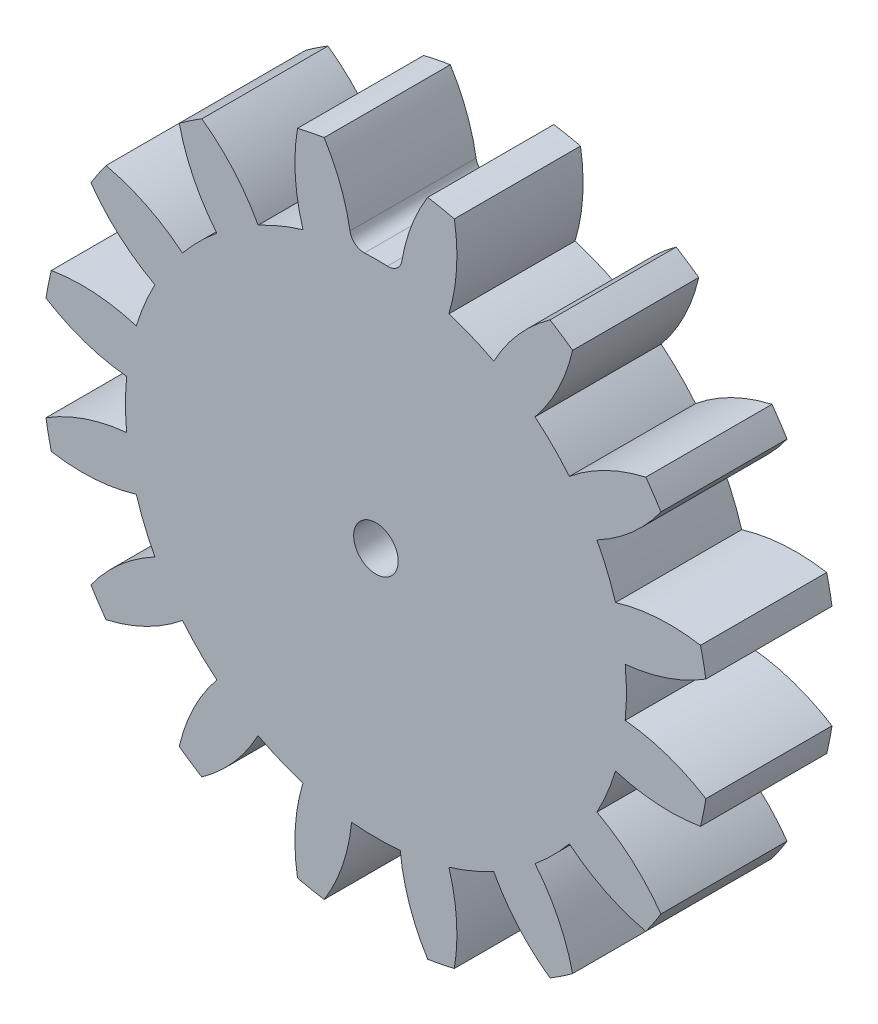
SolidWorks part; units mm, degrees
ref_plane "Front Plane" through (0, 0, 0) normal (0, 0, 1) x (1, 0, 0)
ref_plane "Top Plane" through (0, 0, 0) normal (0, 1, 0) x (1, 0, 0)
ref_plane "Right Plane" through (0, 0, 0) normal (1, 0, 0) x (0, 0, -1)
sketch "Sketch1" plane through (0, 0, 0) normal (0, 0, 1) x (1, 0, 0)
  circle A0 centre (0, 0) radius 22.5
  circle A1 centre (0, 0) radius 1.5
  dimension "D1" = 3
  dimension "D2" = 45
extrude "Boss-Extrude1" add sketch "Sketch1" along normal mid plane 8.5
sketch "Sketch2" plane through (0, 0, 0) normal (0, 0, 1) x (1, 0, 0)
  line L0 (0, 0) -> (0, 22.5) construction
  line L1 (0, 0) -> (-1.6371, 16.7954) construction
  line L2 (0, 13.4531) -> (-2.7041, 20.8825) construction
  arc A0 (2.3332, 19.8634) -> (-2.3332, 19.8634) centre (0, 0) ccw construction
  arc A1 (1.6371, 16.7954) -> (-1.6371, 16.7954) centre (0, 0) ccw
  circle A2 centre (0, 0) radius 22.5 construction
  arc A3 (3.488, 22.228) -> (-3.488, 22.228) centre (0, 0) ccw
  arc A4 (-1.6371, 16.7954) -> (-3.488, 22.228) centre (-14.1001, 15.5806) ccw
  arc A5 (1.6371, 16.7954) -> (3.488, 22.228) centre (14.1001, 15.5806) cw
  dimension "D1" = 40
  dimension "D2" = 5.625
  dimension "D3" = 20
  dimension "D4" = 4.677
extrude "Cut-Extrude1" cut sketch "Sketch2" against normal through all both and the other way through all
fillet "Fillet1" radius 0.95 2 edges at (1.6371, 16.7954, 0) (-1.6371, 16.7954, 0)
pattern_circular "CirPattern3" count 16 over 360 about axis through (0, 0, 4.25) along (0, 0, -1) of "Cut-Extrude1"
equation "\"Module\" = 2.5"
equation "\"Pressure Angle\"= 20"
equation "\"Bore\"= 3"
equation "\"NumTeeth\"= 16"
equation "\"D1@Sketch1\"=\"Bore\""
equation "\"D2@Sketch1\"=(\"NumTeeth\"+2)*\"Module\""
equation "\"D1@Sketch2\"=\"NumTeeth\"*\"Module\""
equation "\"ToothDepth\"= IIF ( \"Module\" < 1.25 , 2.4 * \"Module\" , 2.25 * \"Module\" )"
equation "\"D2@Sketch2\"=\"ToothDepth\""
equation "\"D3@Sketch2\"=\"Pressure Angle\""
equation "\"D4@Sketch2\"=((\"Module\"*PI)/2)+0.3*\"Module\""
equation "\"D1@Fillet1\"=\"Module\"*0.38"
equation "\"D1@CirPattern3\"=\"NumTeeth\""
